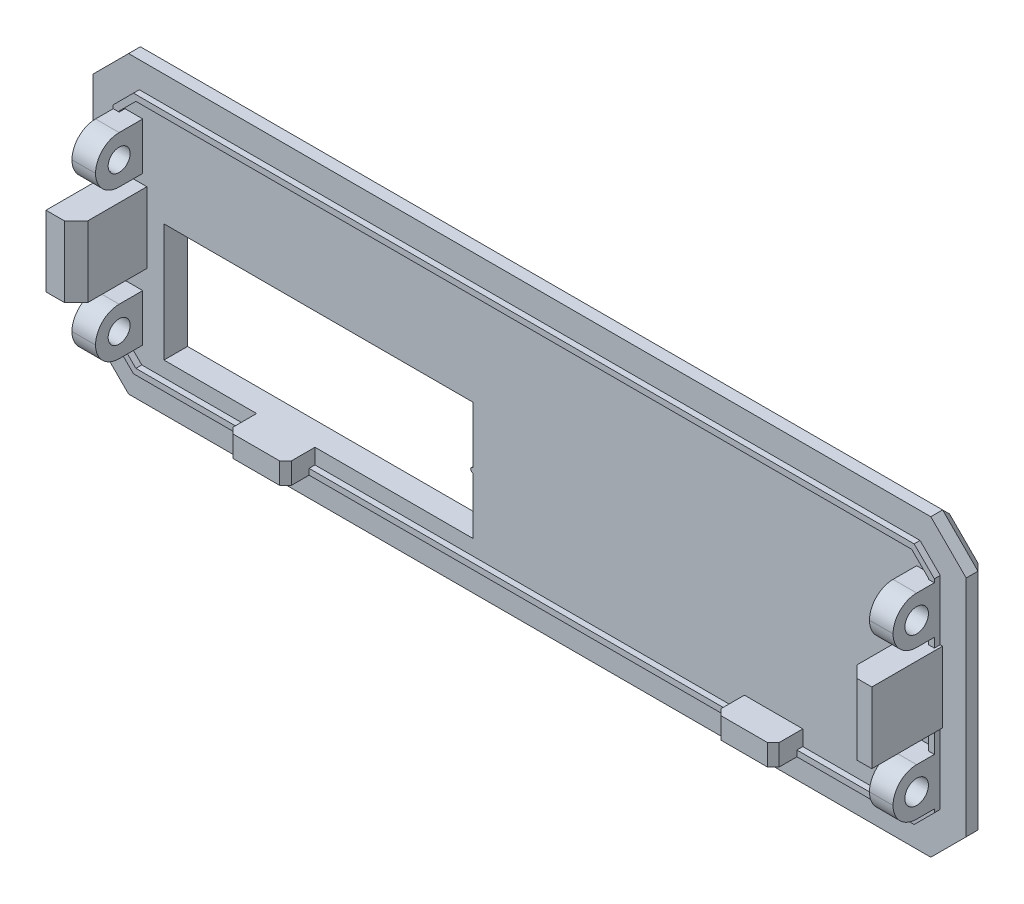
SolidWorks part; units mm, degrees
ref_plane "前视基准面" through (0, 0, 0) normal (0, 0, 1) x (1, 0, 0)
ref_plane "上视基准面" through (0, 0, 0) normal (0, 1, 0) x (1, 0, 0)
ref_plane "右视基准面" through (0, 0, 0) normal (1, 0, 0) x (0, 0, -1)
other "Configuration Table"
sketch "草图1" plane through (0, 0, 0) normal (0, 0, 1) x (1, 0, 0)
  line L0 (-39.7638, 4.7992) -> (-36.7638, 7.7992)
  line L5 (-36.7638, 7.7992) -> (31.2362, 7.7992)
  line L6 (-39.7638, 4.7992) -> (-39.7638, -14.2008)
  line L7 (-36.7638, -17.2008) -> (31.2362, -17.2008)
  line L8 (34.2362, 4.7992) -> (34.2362, -14.2008)
  line L9 (-39.7638, -14.2008) -> (-36.7638, -17.2008)
  line L10 (31.2362, -17.2008) -> (34.2362, -14.2008)
  line L11 (31.2362, 7.7992) -> (34.2362, 4.7992)
  point P0 (-39.7638, 7.7992)
  point P1 (34.2362, -17.2008)
  point P2 (-39.7638, -17.2008)
  point P3 (34.2362, 7.7992)
  dimension "D1" = 74
  dimension "D2" = 25
extrude "凸台-拉伸1" add sketch "草图1" along normal blind 2
chamfer "倒角1" distance 1 angle 45 8 edges at (-38.2638, 6.2992, 0) (-2.7638, -17.2008, 0) (-39.7638, -4.7008, 0) (-38.2638, -15.7008, 0) (32.7362, -15.7008, 0) (34.2362, -4.7008, 0) (32.7362, 6.2992, 0) (-2.7638, 7.7992, 0)
sketch "草图3" plane through (0, 0, 2) normal (0, 0, 1) x (1, 0, 0)
  line L0 (-36.7638, 7.7992) -> (31.2362, 7.7992) construction
  line L1 (-37.5638, 3.5992) -> (-35.5638, 3.5992)
  line L2 (-37.5638, 3.5992) -> (-37.5638, -0.4008)
  line L3 (-37.5638, -0.4008) -> (-35.5638, -0.4008)
  line L4 (-35.5638, 3.5992) -> (-35.5638, -0.4008)
  line L5 (-37.5638, -13.0008) -> (-35.5638, -13.0008)
  line L6 (-37.5638, -13.0008) -> (-37.5638, -9.0008)
  line L7 (-37.5638, -9.0008) -> (-35.5638, -9.0008)
  line L8 (-35.5638, -13.0008) -> (-35.5638, -9.0008)
  line L9 (32.0362, 3.5992) -> (30.0362, 3.5992)
  line L10 (32.0362, 3.5992) -> (32.0362, -0.4008)
  line L11 (32.0362, -0.4008) -> (30.0362, -0.4008)
  line L12 (30.0362, 3.5992) -> (30.0362, -0.4008)
  line L13 (32.0362, -13.0008) -> (30.0362, -13.0008)
  line L14 (32.0362, -13.0008) -> (32.0362, -9.0008)
  line L15 (32.0362, -9.0008) -> (30.0362, -9.0008)
  line L16 (30.0362, -13.0008) -> (30.0362, -9.0008)
  line L17 (-39.7638, -14.2008) -> (-39.7638, 4.7992) construction
  line L18 (34.2362, 4.7992) -> (34.2362, -14.2008) construction
  line L19 (31.2362, -17.2008) -> (-36.7638, -17.2008) construction
  dimension "D1" = 2
  dimension "D2" = 4
  dimension "D3" = 4.2
  dimension "D4" = 2.2
  dimension "D5" = 2.2
  dimension "D6" = 4.2
extrude "凸台-拉伸2" add sketch "草图3" along normal blind 4
fillet "圆角1" radius 2 8 edges at (31.0362, 3.5992, 6) (31.0362, -0.4008, 6) (31.0362, -9.0008, 6) (31.0362, -13.0008, 6) (-36.5638, -13.0008, 6) (-36.5638, -9.0008, 6) (-36.5638, 3.5992, 6) (-36.5638, -0.4008, 6)
sketch "草图4" plane through (32.0362, 0, 0) normal (1, 0, 0) x (0, 0, -1)
  circle A0 centre (-4, 1.5992) radius 1
  circle A1 centre (-4, -11.0008) radius 1
  dimension "D1" = 2
extrude "切除-拉伸1" cut sketch "草图4" against normal up to next (2 mm away) draft 2
sketch "草图5" plane through (-37.5638, 0, 0) normal (-1, 0, 0) x (0, 0, 1)
  circle A0 centre (4, 1.5992) radius 1
  circle A1 centre (4, -11.0008) radius 1
  dimension "D1" = 2
extrude "切除-拉伸2" cut sketch "草图5" against normal up to next (2 mm away) draft 2
sketch "草图8" plane through (0, 0, 2) normal (0, 0, 1) x (1, 0, 0)
  line L0 (-37.7638, 3.9708) -> (-37.7638, -13.3724) construction
  line L1 (-37.7638, -1.2008) -> (-35.2138, -1.2008)
  line L2 (-37.7638, -1.2008) -> (-37.7638, -7.2008)
  line L3 (-37.7638, -7.2008) -> (-35.2138, -7.2008)
  line L4 (-35.2138, -1.2008) -> (-35.2138, -7.2008)
  line L6 (32.2362, -13.3724) -> (32.2362, 3.9708) construction
  line L7 (32.2362, -1.2008) -> (29.9862, -1.2008)
  line L8 (32.2362, -1.2008) -> (32.2362, -7.2008)
  line L9 (32.2362, -7.2008) -> (29.9862, -7.2008)
  line L10 (29.9862, -1.2008) -> (29.9862, -7.2008)
  line L12 (-36.7638, -17.2008) -> (31.2362, -17.2008) construction
  dimension "D1" = 10
  dimension "D2" = 6
  dimension "D3" = 2.55
  dimension "D4" = 2.25
extrude "凸台-拉伸5" add sketch "草图8" along normal blind 6
chamfer "倒角3" distance 1 angle 45 2 edges at (29.9862, -4.2008, 8) (-35.2138, -4.2008, 8)
sketch "草图10" plane through (0, 0, 0) normal (0, 0, -1) x (-1, 0, 0)
  line L0 (36.7638, -17.2008) -> (-31.2362, -17.2008) construction
  line L1 (7.5638, -3.2008) -> (33.7638, -3.2008)
  line L2 (7.5638, -3.2008) -> (7.5638, -13.2008)
  line L3 (7.5638, -13.2008) -> (33.7638, -13.2008)
  line L4 (33.7638, -3.2008) -> (33.7638, -13.2008)
  line L5 (39.7638, 4.7992) -> (39.7638, -14.2008) construction
  dimension "D1" = 4
  dimension "D2" = 10
  dimension "D3" = 6
  dimension "D4" = 26.2
extrude "切除-拉伸3" cut sketch "草图10" against normal up to next
sketch "草图11" plane through (0, 0, 2) normal (0, 0, 1) x (1, 0, 0)
  line L8 (30.1178, 5.0992) -> (-35.6455, 5.0992)
  line L9 (-35.6455, 5.0992) -> (-37.0638, 3.6808)
  line L10 (-37.0638, 3.6808) -> (-37.0638, -13.0824)
  line L11 (-37.0638, -13.0824) -> (-35.6455, -14.5008)
  line L12 (-35.6455, -14.5008) -> (30.1178, -14.5008)
  line L13 (30.1178, -14.5008) -> (31.5362, -13.0824)
  line L14 (31.5362, -13.0824) -> (31.5362, 3.6808)
  line L15 (31.5362, 3.6808) -> (30.1178, 5.0992)
  line L16 (30.3249, 5.5992) -> (-35.8526, 5.5992)
  line L17 (-35.8526, 5.5992) -> (-37.5638, 3.8879)
  line L18 (-37.5638, 3.8879) -> (-37.5638, -13.2895)
  line L19 (-37.5638, -13.2895) -> (-35.8526, -15.0008)
  line L20 (-35.8526, -15.0008) -> (30.3249, -15.0008)
  line L21 (30.3249, -15.0008) -> (32.0362, -13.2895)
  line L22 (32.0362, -13.2895) -> (32.0362, 3.8879)
  line L23 (32.0362, 3.8879) -> (30.3249, 5.5992)
  line L24 (30.3249, 5.5992) -> (-35.8526, 5.5992)
  line L25 (-35.8526, 5.5992) -> (-37.5638, 3.8879)
  line L26 (-37.5638, 3.8879) -> (-37.5638, -13.2895)
  line L27 (-37.5638, -13.2895) -> (-35.8526, -15.0008)
  line L28 (-35.8526, -15.0008) -> (30.3249, -15.0008)
  line L29 (30.3249, -15.0008) -> (32.0362, -13.2895)
  line L30 (32.0362, -13.2895) -> (32.0362, 3.8879)
  line L31 (32.0362, 3.8879) -> (30.3249, 5.5992)
  dimension "D1" = 2.2
  dimension "D2" = 0.5
extrude "凸台-拉伸7" add sketch "草图11" along normal blind 0.5
sketch "草图12" plane through (0, 0, 2) normal (0, 0, 1) x (1, 0, 0)
  line L0 (20.4077, -13.2008) -> (15.4077, -13.2008) construction
  line L1 (15.4362, -13.2008) -> (20.3862, -13.2008)
  line L2 (15.4362, -13.2008) -> (15.4362, -15.0008)
  line L3 (15.4362, -15.0008) -> (20.3862, -15.0008)
  line L4 (20.3862, -13.2008) -> (20.3862, -15.0008)
  line L6 (34.2362, -14.2008) -> (34.2362, 4.7992) construction
  line L7 (-33.7638, -13.2008) -> (-7.5638, -13.2008) construction
  line L8 (-25.9138, -13.2008) -> (-20.9638, -13.2008)
  line L9 (-25.9138, -13.2008) -> (-25.9138, -15.0008)
  line L10 (-25.9138, -15.0008) -> (-20.9638, -15.0008)
  line L11 (-20.9638, -13.2008) -> (-20.9638, -15.0008)
  line L13 (-39.7638, 4.7992) -> (-39.7638, -14.2008) construction
  line L14 (-35.8526, -15.0008) -> (30.3249, -15.0008) construction
  point P6 (15.4362, -15.0008)
  point P16 (-20.9638, -15.0008)
  point P20 (0, 0)
  point P21 (0, 0)
  point P23 (0, 0)
  point P24 (0, 0)
  dimension "D1" = 13.85
  dimension "D2" = 4.95
  dimension "D3" = 13.85
extrude "凸台-拉伸8" add sketch "草图12" along normal blind 2.5
chamfer "倒角4" distance 0.5 angle 45 4 edges at (-25.9138, -14.1008, 4.5) (-20.9638, -14.1008, 4.5) (20.3862, -14.1008, 4.5) (15.4362, -14.1008, 4.5)
sketch "草图13" plane through (0, 0, 0) normal (0, 0, -1) x (-1, 0, 0)
  line L0 (7.5638, -3.2008) -> (7.5638, -13.2008) construction
  circle A0 centre (7.5638, -8.2008) radius 0.2
  dimension "D1" = 0.4
extrude "凸台-拉伸9" add sketch "草图13" against normal blind 2
